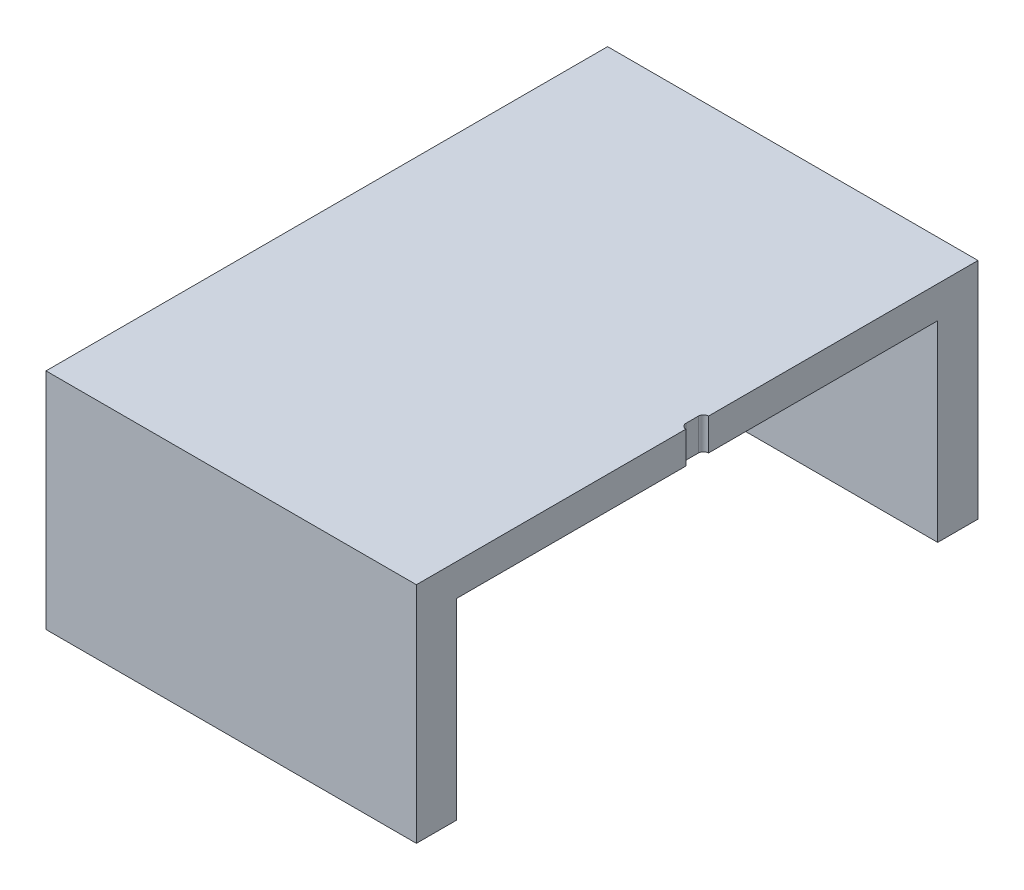
SolidWorks part; units mm, degrees
ref_plane "Front Plane" through (0, 0, 0) normal (0, 0, 1) x (1, 0, 0)
ref_plane "Top Plane" through (0, 0, 0) normal (0, 1, 0) x (1, 0, 0)
ref_plane "Right Plane" through (0, 0, 0) normal (1, 0, 0) x (0, 0, -1)
sketch "MainSketch" plane through (0, 0, 0) normal (0, 1, 0) x (1, 0, 0)
  line L0 (0, -4) -> (-32.75, -4)
  line L1 (0, 0) -> (-36.75, 0)
  line L2 (0, 0) -> (0, -55.72)
  line L3 (0, -55.72) -> (-36.75, -55.72)
  line L4 (-36.75, 0) -> (-36.75, -55.72)
  line L5 (-32.75, -4) -> (-32.75, -51.72)
  line L6 (-32.75, -51.72) -> (0, -51.72)
  line L7 (31.75, -5) -> (-31.75, -5) construction
  line L8 (-31.75, -5) -> (-31.75, -50.72) construction
  line L9 (-31.75, -50.72) -> (31.75, -50.72) construction
  line L10 (0, -27.235) -> (0, -28.485) construction
  line L11 (0.5, -27.235) -> (0.5, -28.485)
  line L12 (-0.5, -27.235) -> (-0.5, -28.485)
  arc A0 (0.5, -27.235) -> (-0.5, -27.235) centre (0, -27.235) ccw
  arc A1 (-0.5, -28.485) -> (0.5, -28.485) centre (0, -28.485) ccw
  point P7 (-10, -2.5)
  point P10 (-34.25, -2.5)
  point P11 (-34.25, -53.22)
  point P12 (-10, -53.22)
  point P17 (0, -27.86)
  point P24 (0, 0)
  point P25 (0, 0)
  point P26 (0, 0)
  dimension "D14" = 0.5
  dimension "D1" = 4
  dimension "D2" = 4
  dimension "D3" = 4
  dimension "D4" = 36.75
  dimension "D6" = 5
  dimension "D7" = 5
  dimension "D8" = 5
  dimension "D9" = 2.5
  dimension "D10" = 2.5
  dimension "D11" = 10
  dimension "D12" = 10
  dimension "D13" = 2.5
  dimension "D15" = 1.25
  dimension "D5" = 45.72
  dimension "D16" = 63.5
extrude "Wall" add sketch "MainSketch" along normal blind 19.05 contours L6 L5 L0 L2 L1 L4 L3 region at (-16.375, 0, 3.3325)
extrude "Roof" add sketch "MainSketch<3>" along normal blind 3.175 from surface contours L5 L6 L2 L0 | L6 L5 L0 L2 L1 L4 L3 region at (-16.3855, 0, 27.86) region at (-16.375, 0, 3.3325) starting at face at (-17.375, 19.05, 27.86)
sketch "MainSketch<3>" plane through (0, 0, 0) normal (0, 1, 0) x (1, 0, 0) same geometry as "MainSketch"
hole_wizard "#2-56 Tapped Hole1" positions "3DSketch1" profile "Sketch2" tap size "#2-56" standard "ANSI Inch"
sketch3d "3DSketch1"
  point P0 (-10, 0, 53.22)
  point P2 (-34.25, 0, 53.22)
  point P4 (-34.25, 0, 2.5)
  point P6 (-10, 0, 2.5)
sketch "Sketch2" plane through (-10, 0, 53.22) normal (1, 0, 0) x (0, 0, -1)
  line L0 (0, 0) -> (0, 6.2642)
  line L1 (0, 6.2642) -> (0.889, 5.73)
  line L2 (0.889, 5.73) -> (0.889, 0)
  line L5 (0.889, 0) -> (0, 0)
  line L10 (0, 6.2642) -> (-0.889, 5.73) construction
  line L11 (0, -6.35) -> (0, 107.95) construction
  dimension "Tap Drill Dia." = 1.778
  dimension "Tap Drill Depth" = 5.73
  dimension "Drill Angle" = 118
cosmetic thread "Hole Thread1" parameters "D1"=4.37, "D2"=2.1844
cosmetic thread "Hole Thread2" parameters "D1"=4.37, "D2"=2.1844
cosmetic thread "Hole Thread3" parameters "D1"=4.37, "D2"=2.1844
cosmetic thread "Hole Thread4" parameters "D1"=4.37, "D2"=2.1844
equation "\"D2@MainSketch\" = \"D1@MainSketch\""
equation "\"D3@MainSketch\" = \"D2@MainSketch\""
equation "\"D7@MainSketch\" = \"D6@MainSketch\""
equation "\"D8@MainSketch\" = \"D6@MainSketch\""
equation "\"D9@MainSketch\" = \"D7@MainSketch\" / 2"
equation "\"D10@MainSketch\" = \"D9@MainSketch\""
equation "\"D12@MainSketch\" = \"D11@MainSketch\""
equation "\"D13@MainSketch\" = \"D10@MainSketch\""
equation "\"D4@MainSketch\"=(\"D16@MainSketch\"+\"D6@MainSketch\"*2)/2"
